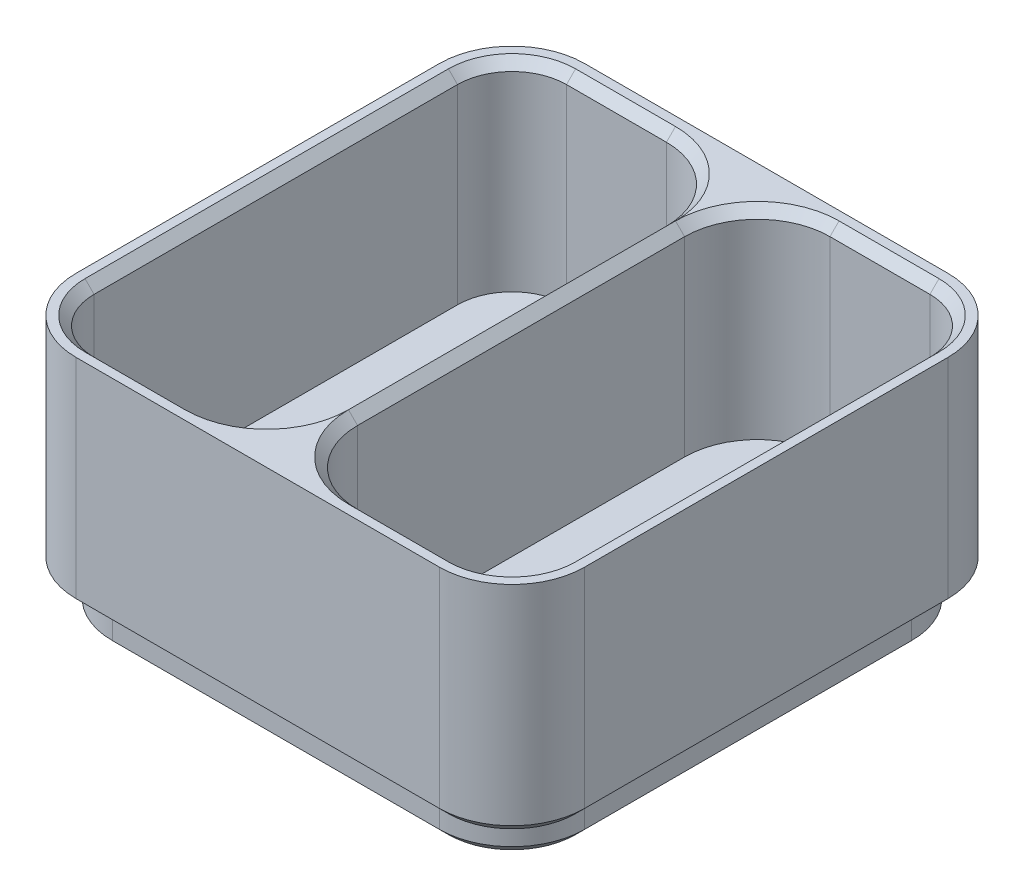
SolidWorks part; units mm, degrees
ref_plane "Front Plane" through (0, 0, 0) normal (0, 0, 1) x (1, 0, 0)
ref_plane "Top Plane" through (0, 0, 0) normal (0, 1, 0) x (1, 0, 0)
ref_plane "Right Plane" through (0, 0, 0) normal (1, 0, 0) x (0, 0, -1)
sketch "Sketch5" plane through (0, 0, 0) normal (0, 1, 0) x (1, 0, 0)
  line L1 (-22.5, -32.5) -> (22.5, -32.5)
  line L2 (-32.5, -22.5) -> (-32.5, 22.5)
  line L3 (-22.5, 32.5) -> (22.5, 32.5)
  line L4 (32.5, -22.5) -> (32.5, 22.5)
  line L5 (-32.5, -32.5) -> (32.5, 32.5) construction
  line L6 (-32.5, 32.5) -> (32.5, -32.5) construction
  arc A0 (-22.5, -32.5) -> (-32.5, -22.5) centre (-22.5, -22.5) cw
  arc A1 (22.5, -32.5) -> (32.5, -22.5) centre (22.5, -22.5) ccw
  arc A2 (22.5, 32.5) -> (32.5, 22.5) centre (22.5, 22.5) cw
  arc A3 (-32.5, 22.5) -> (-22.5, 32.5) centre (-22.5, 22.5) cw
  point P0 (0, 0)
  dimension "D3" = 10
  dimension "D1" = 65
  dimension "D2" = 65
extrude "Boss-Extrude4" add sketch "Sketch5" along normal blind 5
sketch "Sketch6" plane through (0, 5, 0) normal (0, 1, 0) x (1, 0, 0)
  line L1 (35, 35) -> (-35, 35)
  line L2 (35, 35) -> (35, -35)
  line L3 (35, -35) -> (-35, -35)
  line L4 (-35, 35) -> (-35, -35)
  line L5 (35, 35) -> (-35, -35) construction
  line L6 (35, -35) -> (-35, 35) construction
  point P0 (0, 0)
extrude "Boss-Extrude5" add sketch "Sketch6" along normal blind 30
sketch "Sketch8" plane through (0, 0, 0) normal (0, -1, 0) x (1, 0, 0)
  line L0 (-29.5711, 29.5711) -> (-22.5, 22.5)
  arc A0 (-22.5, 32.5) -> (-32.5, 22.5) centre (-22.5, 22.5) ccw construction
  circle A1 centre (-26.0355, 26.0355) radius 3
  circle A2 centre (26.0365, 26.0365) radius 3
  circle A3 centre (26.0375, -26.0355) radius 3
  circle A4 centre (-26.0345, -26.0365) radius 3
  point P8 (0, 0)
  point P15 (0.001, 0.001)
  point P18 (0.002, 0)
  point P21 (0.001, -0.001)
  point P22 (0.001, 0)
  dimension "D1" = 4
extrude "Cut-Extrude1" cut sketch "Sketch8" against normal blind 2 contours A3 | A2 | L0 A1 | L0 A1 | A4 region at (-25.1352, 0, 26.9359) region at (-26.9359, 0, 25.1352) region at (26.0365, 0, 26.0365) region at (26.0375, 0, -26.0355) region at (-26.0345, 0, -26.0365)
fillet "Fillet1" radius 10 4 edges at (-35, 20, -35) (-35, 20, 35) (35, 20, 35) (35, 20, -35)
sketch "Sketch9" plane through (0, 35, 0) normal (0, 1, 0) x (1, 0, 0)
  line L8 (25, 32.5) -> (-25, 32.5)
  line L9 (-32.5, 25) -> (-32.5, -25)
  line L10 (-25, -32.5) -> (25, -32.5)
  line L11 (32.5, -25) -> (32.5, 25)
  line L12 (25, 32.5) -> (-25, 32.5)
  line L13 (-32.5, 25) -> (-32.5, -25)
  line L14 (-25, -32.5) -> (25, -32.5)
  line L15 (32.5, -25) -> (32.5, 25)
  arc A8 (-25, 32.5) -> (-32.5, 25) centre (-25, 25) ccw
  arc A9 (-32.5, -25) -> (-25, -32.5) centre (-25, -25) ccw
  arc A10 (25, -32.5) -> (32.5, -25) centre (25, -25) ccw
  arc A11 (32.5, 25) -> (25, 32.5) centre (25, 25) ccw
  arc A12 (-25, 32.5) -> (-32.5, 25) centre (-25, 25) ccw
  arc A13 (-32.5, -25) -> (-25, -32.5) centre (-25, -25) ccw
  arc A14 (25, -32.5) -> (32.5, -25) centre (25, -25) ccw
  arc A15 (32.5, 25) -> (25, 32.5) centre (25, 25) ccw
  dimension "D1" = 2.5
extrude "Cut-Extrude2" cut sketch "Sketch9" against normal blind 30
sketch "Sketch10" plane through (0, 5, 0) normal (0, -1, 0) x (1, 0, 0)
  line L8 (-35, 25) -> (-35, -25)
  line L9 (-25, -35) -> (25, -35)
  line L10 (35, -25) -> (35, 25)
  line L11 (25, 35) -> (-25, 35)
  line L12 (-35, 25) -> (-35, -25)
  line L13 (-25, -35) -> (25, -35)
  line L14 (35, -25) -> (35, 25)
  line L15 (25, 35) -> (-25, 35)
  arc A8 (-35, -25) -> (-25, -35) centre (-25, -25) ccw
  arc A9 (25, -35) -> (35, -25) centre (25, -25) ccw
  arc A10 (35, 25) -> (25, 35) centre (25, 25) ccw
  arc A11 (-25, 35) -> (-35, 25) centre (-25, 25) ccw
  arc A12 (-35, -25) -> (-25, -35) centre (-25, -25) ccw
  arc A13 (25, -35) -> (35, -25) centre (25, -25) ccw
  arc A14 (35, 25) -> (25, 35) centre (25, 25) ccw
  arc A15 (-25, 35) -> (-35, 25) centre (-25, 25) ccw
  dimension "D1" = 0
extrude "Boss-Extrude6" add sketch "Sketch10" against normal blind 2.5
sketch "Sketch11" plane through (0, 35, 0) normal (0, 1, 0) x (1, 0, 0)
  line L0 (-1.25, -32.5) -> (1.25, -32.5)
  line L1 (25, 32.5) -> (-25, 32.5) construction
  line L3 (-1.25, 32.5) -> (1.25, 32.5)
  line L4 (-25, -32.5) -> (25, -32.5) construction
  line L5 (-1.25, -32.5) -> (-1.25, 32.5)
  line L6 (1.25, -32.5) -> (1.25, 32.5)
extrude "Boss-Extrude7" add sketch "Sketch11" against normal up to surface (27.5 mm away) up to face at (0, 7.5, 0)
fillet "Fillet2" radius 10 4 edges at (1.25, 21.25, -32.5) (1.25, 21.25, 32.5) (-1.25, 21.25, 32.5) (-1.25, 21.25, -32.5)
chamfer "Chamfer1" distance 1.25 angle 45 16 edges at (-32.5, 35, 0) (-30.3033, 35, -30.3033) (-30.3033, 35, 30.3033) (-18.125, 35, -32.5) (-18.125, 35, 32.5) (-4.1789, 35, -29.5711) (-4.1789, 35, 29.5711) (-1.25, 35, 0) (1.25, 35, 0) (4.1789, 35, 29.5711) (4.1789, 35, -29.5711) (18.125, 35, 32.5) (18.125, 35, -32.5) (30.3033, 35, 30.3033) (30.3033, 35, -30.3033) (32.5, 35, 0)
chamfer "Chamfer2" distance 1.25 angle 45 16 edges at (32.0711, 5, 32.0711) (0, 5, 35) (35, 5, 0) (-32.0711, 5, 32.0711) (32.0711, 5, -32.0711) (-35, 5, 0) (0, 5, -35) (-32.0711, 5, -32.0711) (29.5711, 0, 29.5711) (32.5, 0, 0) (0, 0, 32.5) (29.5711, 0, -29.5711) (-29.5711, 0, 29.5711) (0, 0, -32.5) (-32.5, 0, 0) (-29.5711, 0, -29.5711)
